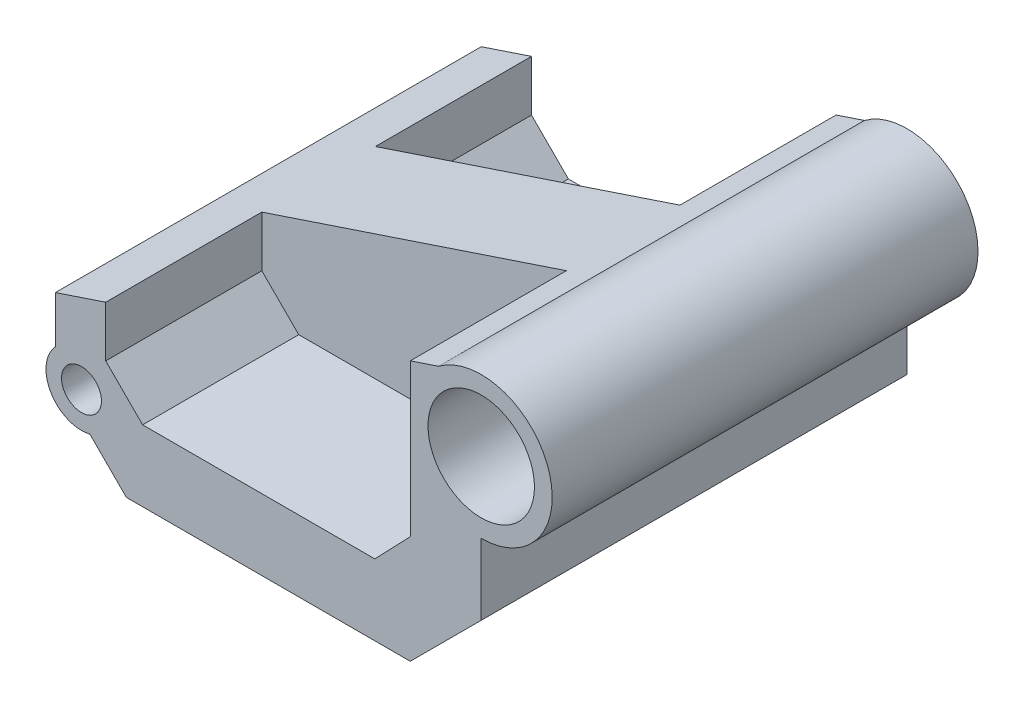
SolidWorks part; units mm, degrees
ref_plane "Front Plane" through (0, 0, 0) normal (0, 0, 1) x (1, 0, 0)
ref_plane "Top Plane" through (0, 0, 0) normal (0, 1, 0) x (1, 0, 0)
ref_plane "Right Plane" through (0, 0, 0) normal (1, 0, 0) x (0, 0, -1)
sketch "Sketch1" plane through (0, 0, 0) normal (0, 1, 0) x (1, 0, 0)
  line L1 (0, 25.6548) -> (101.6, 25.6548)
  line L2 (0, 25.6548) -> (0, -25.1452)
  line L3 (0, -25.1452) -> (101.6, -25.1452)
  line L4 (101.6, 25.6548) -> (101.6, -25.1452)
  dimension "D1" = 101.6
  dimension "D2" = 50.8
sketch "Sketch2" plane through (0, 0, 0) normal (1, 0, 0) x (0, 0, -1)
  line L0 (25.6548, 0) -> (-25.1452, 0) construction
  line L1 (26.2506, 50.8) -> (-24.5494, 50.8)
  line L2 (26.2506, 50.8) -> (26.2506, 0)
  line L3 (26.2506, 0) -> (-24.5494, 0)
  line L4 (-24.5494, 50.8) -> (-24.5494, 0)
  dimension "D1" = 50.8
  dimension "D2" = 50.8
  dimension "D3" = 0
sketch "Sketch4" plane through (0, 0, 0) normal (0, 0, 1) x (1, 0, 0)
  line L0 (0, 0) -> (101.6, 0) construction
  line L1 (0, 0) -> (101.6, 0)
  line L2 (0, 0) -> (0, 50.8)
  line L3 (0, 50.8) -> (101.6, 50.8)
  line L4 (101.6, 0) -> (101.6, 50.8)
  line L5 (0, 50.8) -> (0, 0) construction
  line L6 (25.4, 1.4046) -> (25.4, 14.1046)
  line L7 (25.4, 14.1046) -> (63.5, 26.8046)
  line L8 (63.5, 26.8046) -> (63.5, 1.4046)
  line L10 (25.4, 1.4046) -> (63.5, 1.4046)
  dimension "D1" = 0
  dimension "D2" = 50.8
  dimension "D3" = 101.6
  dimension "D4" = 0
  dimension "D5" = 38.1
  dimension "D6" = 25.4
  dimension "D7" = 12.7
  dimension "D8" = 25.4
extrude "Boss-Extrude1" add sketch "Sketch4" along normal blind 19.05 and the other way blind 19.05 contours L7 L8 L10 L6
sketch "Sketch5" plane through (0, 0, 19.05) normal (0, 0, 1) x (1, 0, 0)
  line L0 (63.5, 26.8046) -> (63.5, 1.4046) construction
  circle A0 centre (63.5, 20.4546) radius 6.35
  point P2 (63.5, 26.8046)
  point P3 (64.145, 23.6877)
  point P4 (61.8133, 26.8046)
  point P5 (0, 0)
  point P6 (0, 0)
  point P7 (65.1867, 22.1456)
  point P8 (0, 0)
  dimension "D3" = 12.7
  dimension "D1" = 6.35
  dimension "D2" = 0
extrude "Boss-Extrude2" add sketch "Sketch5" against normal up to surface (38.1 mm away) up to face at (44.45, 10.9296, -19.05)
hole_wizard "3/8 (0.375) Diameter Hole1" positions "Sketch8" profile "Sketch9" hole size "3/8" standard "ANSI Inch" end condition through all
sketch "Sketch8" plane through (0, 0, 19.05) normal (0, 0, 1) x (1, 0, 0)
  point P0 (63.5, 20.4546)
sketch "Sketch9" plane through (63.5, 20.4546, 19.05) normal (1, 0, 0) x (0, -1, 0)
  line L0 (0, 0) -> (0, 38.1)
  line L1 (0, 38.1) -> (4.7625, 38.1)
  line L2 (4.7625, 38.1) -> (4.7625, 0)
  line L5 (4.7625, 0) -> (0, 0)
  line L11 (0, -6.35) -> (0, 107.95) construction
  dimension "Thru Hole Dia." = 9.525
  dimension "Thru Hole Depth" = 38.1
sketch "Sketch11" plane through (0, 0, 19.05) normal (0, 0, 1) x (1, 0, 0)
  line L0 (63.5, 7.7546) -> (57.15, 1.4046)
  line L1 (63.5, 14.1046) -> (63.5, 1.4046) construction
  line L2 (25.4, 1.4046) -> (63.5, 1.4046) construction
  line L3 (57.15, 1.4046) -> (63.5, 1.4046)
  line L4 (63.5, 1.4046) -> (63.5, 7.7546)
  line L5 (25.4, 7.7546) -> (31.75, 1.4046)
  line L6 (25.4, 1.4046) -> (25.4, 14.1046) construction
  line L7 (31.75, 1.4046) -> (25.4, 1.4046)
  line L8 (25.4, 1.4046) -> (25.4, 7.7546)
  dimension "D1" = 6.35
  dimension "D2" = 6.35
extrude "Cut-Extrude2" cut sketch "Sketch11" against normal up to surface (38.1 mm away) contours L0 L3 L4 up to face at (49.0838, 11.8392, -19.05)
sketch "Sketch19" plane through (0, 0, 19.05) normal (0, 0, 1) x (1, 0, 0)
  line L0 (29.8997, 7.7546) -> (57.15, 7.7546)
  line L1 (25.4, 1.4046) -> (63.5, 1.4046) construction
  line L2 (63.5, 26.8046) -> (63.5, 1.4046) construction
  line L3 (57.15, 7.7546) -> (57.15, 24.6879)
  line L4 (25.4, 14.1046) -> (63.5, 26.8046) construction
  line L5 (57.15, 24.6879) -> (29.8997, 15.6045)
  line L6 (29.8997, 15.6045) -> (29.8997, 7.7546)
  line L7 (57.15, 11.0566) -> (53.975, 7.7546)
  line L8 (53.975, 7.7546) -> (57.15, 7.7546)
  line L9 (57.15, 11.0566) -> (57.15, 7.7546)
  dimension "D1" = 6.35
  dimension "D2" = 6.35
  dimension "D3" = 3.175
  dimension "D4" = 3.302
sketch "Sketch20" plane through (0, 0, 19.05) normal (0, 0, 1) x (1, 0, 0)
  line L1 (29.8997, 7.7546) -> (53.975, 7.7546)
  line L2 (53.975, 7.7546) -> (57.15, 11.0566)
  line L3 (57.15, 11.0566) -> (57.15, 24.6879)
  line L4 (57.15, 24.6879) -> (29.8997, 15.6045)
  line L5 (29.8997, 15.6045) -> (29.8997, 7.7546)
extrude "Cut-Extrude5" cut sketch "Sketch20" against normal blind 13.97
sketch "Sketch21" plane through (0, 0, -19.05) normal (0, 0, -1) x (-1, 0, 0)
  line L0 (-57.15, 24.6879) -> (-57.15, 11.0566)
  line L1 (-57.15, 11.0566) -> (-53.975, 7.7546)
  line L2 (-53.975, 7.7546) -> (-29.8997, 7.7546)
  line L3 (-29.8997, 7.7546) -> (-29.8997, 15.6045)
  line L4 (-29.8997, 15.6045) -> (-57.15, 24.6879)
extrude "Cut-Extrude6" cut sketch "Sketch21" against normal blind 13.97
extrude "Cut-Extrude7" cut sketch "Sketch11<4>" against normal through all contours L5 L7 L8
sketch "Sketch11<4>" plane through (0, 0, 19.05) normal (0, 0, 1) x (1, 0, 0) same geometry as "Sketch11"
sketch "Sketch22" plane through (0, 0, 19.05) normal (0, 0, 1) x (1, 0, 0)
  line L0 (33.2017, 7.7546) -> (29.8997, 11.0566)
  line L1 (29.8997, 7.7546) -> (53.975, 7.7546) construction
  line L2 (29.8997, 15.6045) -> (29.8997, 7.7546) construction
  line L3 (29.8997, 11.0566) -> (29.8997, 7.7546)
  line L4 (29.8997, 7.7546) -> (33.2017, 7.7546)
  dimension "D1" = 3.302
  dimension "D2" = 3.302
extrude "Boss-Extrude5" add sketch "Sketch22" against normal up to surface (38.1 mm away) up to face at (68.2625, 20.4546, -19.05)
sketch "Sketch23" plane through (0, 0, 19.05) normal (0, 0, 1) x (1, 0, 0)
  line L0 (31.75, 1.4046) -> (57.15, 1.4046) construction
  line L1 (25.4, 7.7546) -> (31.75, 1.4046) construction
  line L2 (25.4, 7.7546) -> (25.4, 14.1046) construction
  circle A0 centre (27.7318, 7.7546) radius 3.175
  arc A1 (28.575, 4.5796) -> (25.4, 10.0685) centre (27.7318, 7.7546) cw
  point P11 (27.7318, 7.7546)
  line M6 (25.4, 14.1046) -> (25.4, 7.7546)
  line M7 (25.4, 7.7546) -> (31.75, 1.4046)
  dimension "D1" = 6.35
  dimension "D2" = 6.35
extrude "Boss-Extrude6" add sketch "Sketch23" against normal up to surface (38.1 mm away) contours A0 M6 M7 region at (25.9892, 6.5042, 19.05) up to face at (45.815, 11.74, -19.05)
hole_wizard "9/64 (0.14063) Diameter Hole2" positions "3DSketch3" profile "Sketch24" hole size "9/64" standard "ANSI Inch" end condition through all
sketch3d "3DSketch3"
  point P0 (27.7318, 7.7546, 19.05)
sketch "Sketch24" plane through (27.7318, 7.7546, 19.05) normal (1, 0, 0) x (0, -1, 0)
  line L0 (0, 0) -> (0, 38.1)
  line L1 (0, 38.1) -> (1.786, 38.1)
  line L2 (1.786, 38.1) -> (1.786, 0)
  line L5 (1.786, 0) -> (0, 0)
  line L11 (0, -6.35) -> (0, 107.95) construction
  dimension "Thru Hole Dia." = 3.572
  dimension "Thru Hole Depth" = 38.1
sketch "Sketch25" plane through (0, 0, 0) normal (0, 0, 1) x (1, 0, 0)
  circle A0 centre (27.7318, 7.7546) radius 3.302
extrude "Cut-Extrude8" cut sketch "Sketch25" against normal blind 12.7 and the other way blind 12.7
sketch "Sketch26" plane through (25.4, 0, 0) normal (-1, 0, 0) x (0, 0, 1)
  line L0 (-19.05, 14.1046) -> (19.05, 14.1046) construction
  line L1 (-1.27, 14.1046) -> (1.27, 14.1046)
  line L2 (-1.27, 14.1046) -> (-1.27, 10.0925)
  line L3 (-1.27, 10.0925) -> (1.27, 10.0925)
  line L4 (1.27, 14.1046) -> (1.27, 10.0925)
  line L5 (12.7, 10.0925) -> (-12.7, 10.0925) construction
  line L6 (-5.08, 15.6045) -> (-5.08, 24.6879) construction
  dimension "D1" = 2.54
  dimension "D2" = 3.81
sketch "Sketch28" plane through (25.4, 0, 0) normal (-1, 0, 0) x (0, 0, 1)
  line L1 (-1.27, 14.1046) -> (1.27, 14.1046)
  line L2 (-1.27, 14.1046) -> (-1.27, 10.0925)
  line L3 (-1.27, 10.0925) -> (1.27, 10.0925)
  line L4 (1.27, 14.1046) -> (1.27, 10.0925)
extrude "Cut-Extrude9" cut sketch "Sketch28" against normal up to surface (4.4997 mm away) up to face at (29.8997, 13.3306, 12.065)
sketch "Sketch30" plane through (0, 0, 19.05) normal (0, 0, 1) x (1, 0, 0)
  circle A0 centre (63.5, 20.4546) radius 6.35
  point P0 (63.5, 20.4546)
